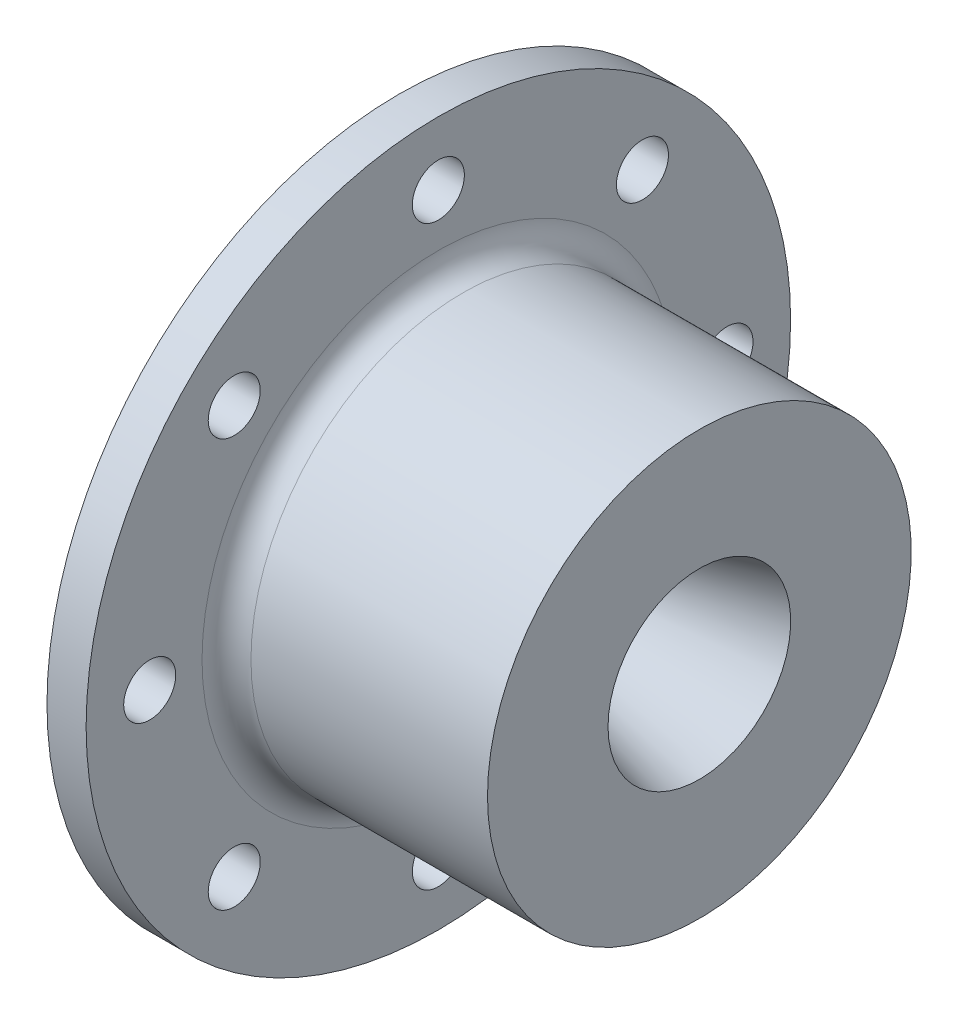
SolidWorks part; units mm, degrees
ref_plane "Front Plane" through (0, 0, 0) normal (0, 0, 1) x (1, 0, 0)
ref_plane "Top Plane" through (0, 0, 0) normal (0, 1, 0) x (1, 0, 0)
ref_plane "Right Plane" through (0, 0, 0) normal (1, 0, 0) x (0, 0, -1)
sketch "Sketch1" plane through (0, 0, 0) normal (0, 0, 1) x (1, 0, 0)
  line L20 (0, 0) -> (32.997, 0) construction
  line L33 (15.2881, 7.1803) -> (21.5111, 7.1803)
  line L34 (15.2881, 7.1803) -> (0, 25.4)
  line L37 (0, 25.4) -> (0, 66.87)
  line L38 (0, 66.87) -> (5.08, 66.87)
  line L39 (5.08, 66.87) -> (5.08, 27.5)
  line L43 (38.9578, 27.5) -> (38.9578, 11.8552)
  line L52 (38.9578, 11.8552) -> (21.5111, 7.1803)
  line L53 (38.9578, 27.5) -> (5.08, 27.5)
  point P1 (2.54, 66.87)
  point P12 (15.2881, 7.1803)
  point P24 (21.5111, 7.1803)
  dimension "D1" = 7.1803
  dimension "D2" = 25.4
  dimension "D5" = 5.08
  dimension "D10" = 15
  dimension "D8" = 11.8552
  dimension "D3" = 27.5
  dimension "D4" = 66.87
  dimension "D6" = 6.223
  dimension "D7" = 50
revolve "Nozzle" add sketch "Sketch1" angle 360 about L20
fillet "Rao outlet radius" radius 2.7429 1 edges at (21.5111, 0, 7.1803)
sketch "Sketch2" plane through (0, 0, 0) normal (-1, 0, 0) x (0, 0, 1)
  point P0 (37.465, 0)
  point P1 (26.4918, -26.4918)
  point P5 (0, -37.465)
  point P6 (-26.4918, -26.4918)
  point P7 (-37.465, 0)
  point P8 (-26.4918, 26.4918)
  point P9 (0, 37.465)
  point P10 (26.4918, 26.4918)
  point P11 (0, 0)
  dimension "D1" = 37.465
  dimension "D2" = 8
hole_wizard "1/4 Clearance Hole1" positions "Sketch2" profile "Sketch3" hole size "1/4" standard "ANSI Inch" end condition through all
sketch "Sketch3" plane through (0, 0, 37.465) normal (0, 1, 0) x (0, 0, 1)
  line L0 (0, 0) -> (0, 38.9578)
  line L1 (0, 38.9578) -> (3.3782, 38.9578)
  line L2 (3.3782, 38.9578) -> (3.3782, 0)
  line L5 (3.3782, 0) -> (0, 0)
  line L11 (0, -6.35) -> (0, 107.95) construction
  dimension "Thru Hole Dia." = 6.7564
  dimension "Thru Hole Depth" = 38.9578
sketch "Sketch5" plane through (0, 0, 0) normal (1, 0, 0) x (0, 0, -1)
  circle A107 centre (0, 0) radius 45.72
  dimension "D1" = 91.44
extrude "Cut-Extrude1" cut sketch "Sketch5" along normal up to surface (5.08 mm away) flip side to cut up to face at (5.08, 0, 40.8432)
fillet "Fillet1" radius 3.175 1 edges at (5.08, 0, 27.5)
fillet "Rao Inlet radius" radius 10.7705 1 edges at (15.2881, 0, 7.1803)
equation "\"radius\"= 1in"
equation "\"Flange\"= 0.55in"
equation "\"Length\"= 2cm"
equation "\"Flange_Thickness\"= 0.2in"
equation "\"offset\"= 0.625cm"
equation "\"D2@Sketch1\"=\"radius\""
equation "\"throat\" = 0.28269in"
equation "\"hole_dia\"= 0.66cm"
equation "\"D1@Sketch1\"=\"throat\""
equation "\"D5@Sketch1\"=\"Flange_Thickness\""
equation "\"Seal_dia\"= 2.5cm"
equation "\"Seal_depth\"= 0.1cm"
equation "\"Seal_width\"= 0.15cm"
equation "\"Nozzle_angle\"= 15"
equation "\"D10@Sketch1\"=\"Nozzle_angle\""
equation "\"nozzle_length\"= 6.34"
equation "\"bolt_head_dia\"=2.3795"
equation "\"bolt_rad\"= \"radius\" + 0.5 * \"Flange\" + 0.2in"
equation "\"scallop_inner_dia\"= 3.3in"
equation "\"exit_rad\"= 1.693cm"
equation "\"D8@Sketch1\"=\"throat\"*(2.726)^0.5"
equation "\"outside_dia\"= 2.75cm"
equation "\"D3@Sketch1\"=\"outside_dia\""
equation "\"D4@Sketch1\"=\"outside_dia\"+\"Flange\"+\"Buffer\""
equation "\"Scallop_OD\"= 0.6in"
equation "\"D3\"= \"Scallop_OD\" / 2"
equation "\"D4\"= \"scallop_inner_dia\" / 2"
equation "\"D1@Sketch2\"=\"bolt_rad\""
equation "\"Buffer\"= 1in"
equation "\"D1@Rao Inlet radius\"=3*\"throat\""
equation "\"D1@Rao outlet radius\"= 0.382 * \"throat\""
equation "\"D1@Rao Inlet radius\"=1.5*\"throat\""
